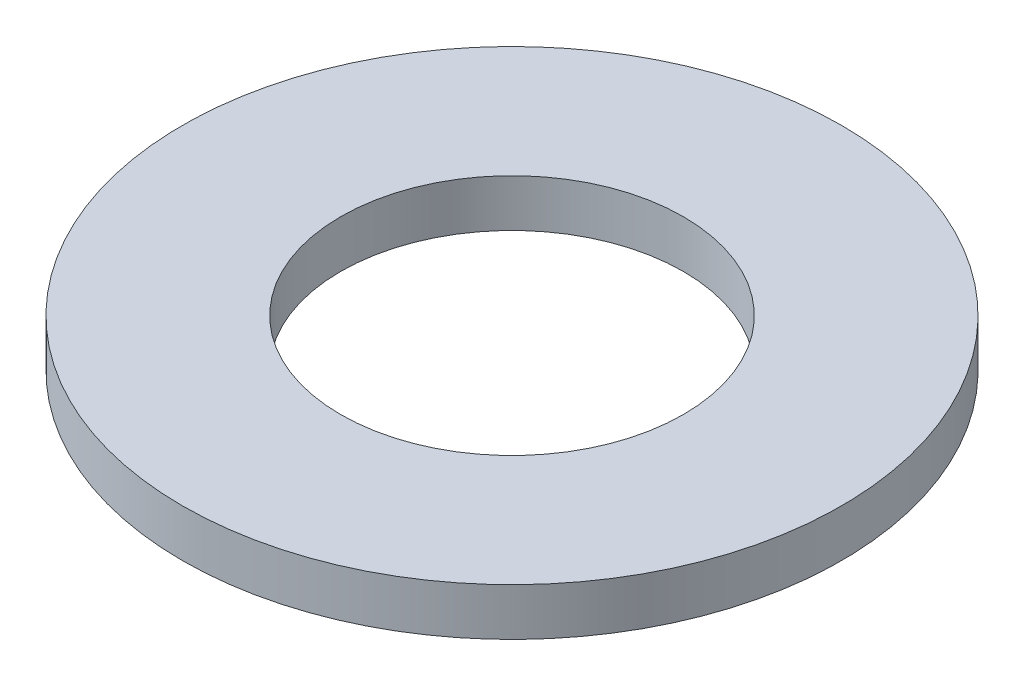
SolidWorks part; units mm, degrees
ref_plane "Front Plane" through (0, 0, 0) normal (0, 0, 1) x (1, 0, 0)
ref_plane "Top Plane" through (0, 0, 0) normal (0, 1, 0) x (1, 0, 0)
ref_plane "Right Plane" through (0, 0, 0) normal (1, 0, 0) x (0, 0, -1)
sketch "Sketch1" plane through (0, 0, 0) normal (0, 1, 0) x (1, 0, 0)
  circle A0 centre (0, 0) radius 62.5
  dimension "FLANGE_OD" = 125
extrude "Boss-Extrude1" add sketch "Sketch1" along normal blind 9
sketch "Sketch2" plane through (0, 0, 0) normal (0, 1, 0) x (1, 0, 0)
  circle A0 centre (0, 0) radius 32.5
  dimension "BORE_D" = 65
extrude "Cut-Extrude1" cut sketch "Sketch2" along normal through all
sketch "Sketch3" plane through (0, 9, 0) normal (0, 1, 0) x (1, 0, 0)
  circle A0 centre (0, 0) radius 24.3245 construction
  circle A1 centre (-24.3245, 0) radius 2.4714
  dimension "BOLT_D" = 4.9429
  dimension "BOLT_PCD" = 48.649
extrude "Cut-Extrude2" cut sketch "Sketch3" against normal blind 6.7814 rebuild error yes
pattern_circular "CirPattern1" count 5 over 360 rebuild error yes
